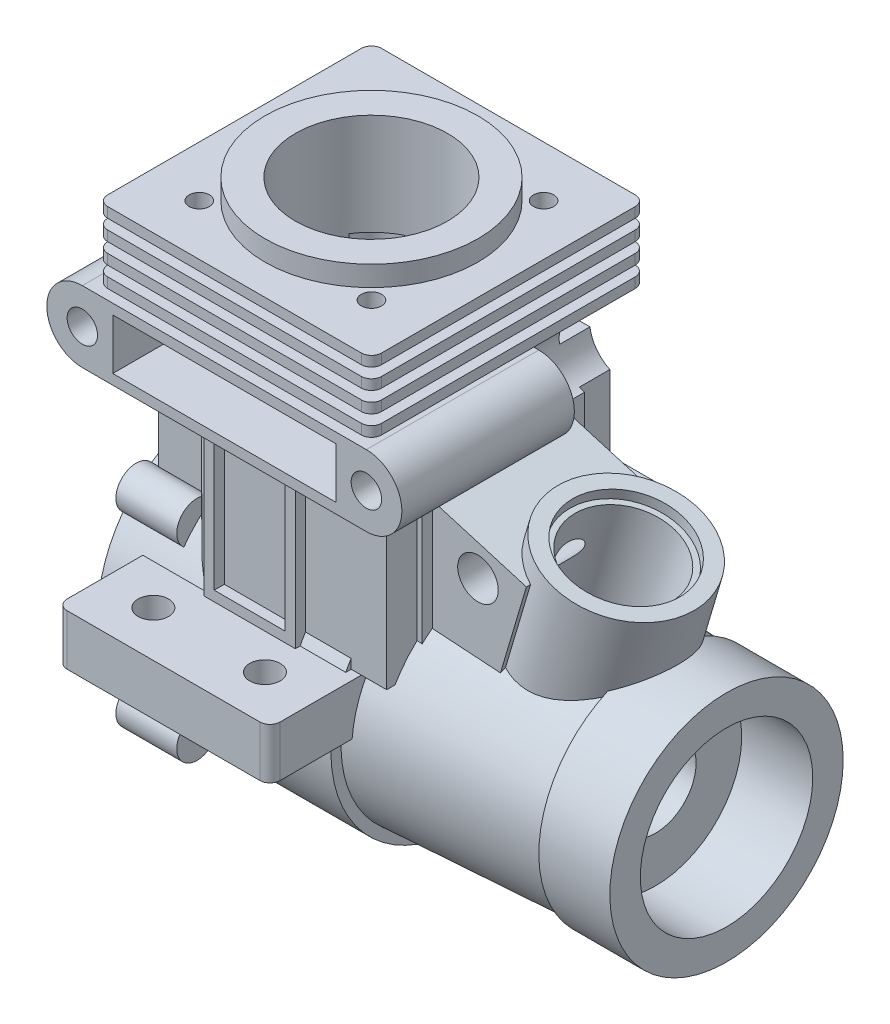
SolidWorks part; units mm, degrees
material "Gray Cast Iron"
ref_plane "Front" through (0, 0, 0) normal (0, 0, 1) x (1, 0, 0)
ref_plane "Top" through (0, 0, 0) normal (0, 1, 0) x (1, 0, 0)
ref_plane "Right" through (0, 0, 0) normal (1, 0, 0) x (0, 0, -1)
sketch "Sketch1" plane through (0, 0, 0) normal (0, 1, 0) x (1, 0, 0)
  line L1 (-13.5, 13.5) -> (13.5, 13.5)
  line L2 (-13.5, 13.5) -> (-13.5, -13.5)
  line L3 (-13.5, -13.5) -> (13.5, -13.5)
  line L4 (13.5, 13.5) -> (13.5, -13.5)
  line L5 (-13.5, 13.5) -> (13.5, -13.5) construction
  line L6 (-13.5, -13.5) -> (13.5, 13.5) construction
  point P0 (0, 0)
extrude "Boss-Extrude2" add sketch "Sketch1" along normal blind 1
sketch "Sketch3" plane through (0, 1, 0) normal (0, 1, 0) x (1, 0, 0)
  line L1 (11.5, 11.5) -> (-11.5, 11.5)
  line L2 (11.5, 11.5) -> (11.5, -11.5)
  line L3 (11.5, -11.5) -> (-11.5, -11.5)
  line L4 (-11.5, 11.5) -> (-11.5, -11.5)
  line L5 (11.5, 11.5) -> (-11.5, -11.5) construction
  line L6 (11.5, -11.5) -> (-11.5, 11.5) construction
  point P0 (0, 0)
extrude "Boss-Extrude3" add sketch "Sketch3" along normal blind 1
sketch "Sketch4" plane through (0, 2, 0) normal (0, 1, 0) x (1, 0, 0)
  line L1 (13.5, -13.5) -> (-13.5, -13.5)
  line L2 (13.5, -13.5) -> (13.5, 13.5)
  line L3 (13.5, 13.5) -> (-13.5, 13.5)
  line L4 (-13.5, -13.5) -> (-13.5, 13.5)
  line L5 (13.5, -13.5) -> (-13.5, 13.5) construction
  line L6 (13.5, 13.5) -> (-13.5, -13.5) construction
  point P0 (0, 0)
extrude "Boss-Extrude4" add sketch "Sketch4" along normal blind 1
sketch "Sketch5" plane through (0, 3, 0) normal (0, 1, 0) x (1, 0, 0)
  line L1 (11.5, -11.5) -> (-11.5, -11.5)
  line L2 (11.5, -11.5) -> (11.5, 11.5)
  line L3 (11.5, 11.5) -> (-11.5, 11.5)
  line L4 (-11.5, -11.5) -> (-11.5, 11.5)
  line L5 (11.5, -11.5) -> (-11.5, 11.5) construction
  line L6 (11.5, 11.5) -> (-11.5, -11.5) construction
  point P0 (0, 0)
extrude "Boss-Extrude5" add sketch "Sketch5" along normal blind 1
sketch "Sketch6" plane through (0, 4, 0) normal (0, 1, 0) x (1, 0, 0)
  line L1 (13.5, -13.5) -> (-13.5, -13.5)
  line L2 (13.5, -13.5) -> (13.5, 13.5)
  line L3 (13.5, 13.5) -> (-13.5, 13.5)
  line L4 (-13.5, -13.5) -> (-13.5, 13.5)
  line L5 (13.5, -13.5) -> (-13.5, 13.5) construction
  line L6 (13.5, 13.5) -> (-13.5, -13.5) construction
  point P0 (0, 0)
extrude "Boss-Extrude6" add sketch "Sketch6" along normal blind 1
sketch "Sketch7" plane through (0, 5, 0) normal (0, 1, 0) x (1, 0, 0)
  line L1 (11.5, -11.5) -> (-11.5, -11.5)
  line L2 (11.5, -11.5) -> (11.5, 11.5)
  line L3 (11.5, 11.5) -> (-11.5, 11.5)
  line L4 (-11.5, -11.5) -> (-11.5, 11.5)
  line L5 (11.5, -11.5) -> (-11.5, 11.5) construction
  line L6 (11.5, 11.5) -> (-11.5, -11.5) construction
  point P0 (0, 0)
  dimension "D1" = 23
  dimension "D2" = 23
extrude "Boss-Extrude7" add sketch "Sketch7" along normal blind 1
sketch "Sketch8" plane through (0, 6, 0) normal (0, 1, 0) x (1, 0, 0)
  line L1 (13.5, -13.5) -> (-13.5, -13.5)
  line L2 (13.5, -13.5) -> (13.5, 13.5)
  line L3 (13.5, 13.5) -> (-13.5, 13.5)
  line L4 (-13.5, -13.5) -> (-13.5, 13.5)
  line L5 (13.5, -13.5) -> (-13.5, 13.5) construction
  line L6 (13.5, 13.5) -> (-13.5, -13.5) construction
  point P0 (0, 0)
extrude "Boss-Extrude8" add sketch "Sketch8" along normal blind 1
fillet "Fillet1" radius 1 28 edges at (-13.5, 0.5, 13.5) (-11.5, 1.5, 11.5) (-13.5, 2.5, 13.5) (-11.5, 3.5, 11.5) (-13.5, 4.5, 13.5) (-11.5, 5.5, 11.5) (-13.5, 6.5, 13.5) (13.5, 0.5, 13.5) (11.5, 1.5, 11.5) (13.5, 2.5, 13.5) (11.5, 3.5, 11.5) (13.5, 4.5, 13.5) (11.5, 5.5, 11.5) (13.5, 6.5, 13.5) (13.5, 0.5, -13.5) (11.5, 1.5, -11.5) (13.5, 2.5, -13.5) (11.5, 3.5, -11.5) (13.5, 4.5, -13.5) (11.5, 5.5, -11.5) (13.5, 6.5, -13.5) (-13.5, 0.5, -13.5) (-11.5, 1.5, -11.5) (-13.5, 2.5, -13.5) (-11.5, 3.5, -11.5) (-13.5, 4.5, -13.5) (-11.5, 5.5, -11.5) (-13.5, 6.5, -13.5)
ref_plane "Plane1" through (0, 0, 14.5) normal (0, 0, 1) x (1, 0, 0)
sketch "Sketch10" plane through (0, 0, 14.5) normal (0, 0, 1) x (1, 0, 0)
  line L3 (-14, -3.5) -> (14, -3.5) construction
  line L4 (-14, 0) -> (14, 0)
  line L5 (-14, -7) -> (14, -7)
  arc A0 (-14, 0) -> (-14, -7) centre (-14, -3.5) ccw
  arc A1 (14, -7) -> (14, 0) centre (14, -3.5) ccw
  point P5 (0, -3.5)
extrude "Boss-Extrude11" add sketch "Sketch10" against normal blind 17
sketch "Sketch12" plane through (0, 0, 14.5) normal (0, 0, 1) x (1, 0, 0)
  line L0 (0, 0) -> (0, -3.5) construction
  line L1 (0, -3.5) -> (14, -3.5) construction
  line L2 (0, -3.5) -> (-14, -3.5) construction
  circle A0 centre (-14, -3.5) radius 1.5
  circle A1 centre (14, -3.5) radius 1.5
  dimension "D1" = 3.5
  dimension "D2" = 14
  dimension "D3" = 14
extrude "Cut-Extrude1" cut sketch "Sketch12" against normal blind 17
ref_plane "Plane2" through (0, -7, 0) normal (0, -1, 0) x (-1, 0, 0)
sketch "Sketch13" plane through (0, -7, 0) normal (0, -1, 0) x (-1, 0, 0)
  line L1 (-13, 8) -> (13, 8)
  line L2 (-13, 8) -> (-13, -8)
  line L3 (-13, -8) -> (13, -8)
  line L4 (13, 8) -> (13, -8)
  line L5 (-13, 8) -> (13, -8) construction
  line L6 (-13, -8) -> (13, 8) construction
  point P0 (0, 0)
extrude "Boss-Extrude13" add sketch "Sketch13" along normal blind 22 and the other way blind 7
ref_plane "Plane4" through (0, 0, -8) normal (0, 0, -1) x (-1, 0, 0)
sketch "Sketch16" plane through (0, 0, -8) normal (0, 0, -1) x (-1, 0, 0)
  circle A0 centre (-14, -3.5) radius 3.5
  circle A1 centre (14, -3.5) radius 3.5
extrude "Cut-Extrude2" cut sketch "Sketch16" against normal blind 5.5
ref_plane "Plane7" through (0, -1, 0) normal (0, -1, 0) x (-1, 0, 0)
sketch "Sketch21" plane through (0, -1, 0) normal (0, -1, 0) x (-1, 0, 0)
  line L1 (13, 8) -> (-13, 8) construction
  line L3 (-9.5, 8) -> (-9.5, 13.5)
  line L4 (-12.5, 13.5) -> (12.5, 13.5) construction
  line L5 (-9.5, 13.5) -> (9.5, 13.5)
  line L6 (9.5, 13.5) -> (9.5, 8)
  line L7 (-9.5, 8) -> (9.5, 8)
extrude "Boss-Extrude16" add sketch "Sketch21" along normal blind 1
ref_plane "Plane8" through (0, -3, 0) normal (0, -1, 0) x (-1, 0, 0)
sketch "Sketch22" plane through (0, -3, 0) normal (0, -1, 0) x (-1, 0, 0)
  line L0 (-9.5, 8) -> (-9.5, 13.5)
  line L1 (13, 8) -> (-13, 8) construction
  line L2 (-9.5, 8) -> (9.5, 8) construction
  line L3 (9.5, 13.5) -> (-9.5, 13.5) construction
  line L4 (-9.5, 13.5) -> (-9.5, 8) construction
  line L5 (-9.5, 13.5) -> (9.5, 13.5)
  line L6 (-12.5, 13.5) -> (12.5, 13.5) construction
  line L7 (9.5, 13.5) -> (9.5, 8)
  line L8 (13, 8) -> (-13, 8) construction
  line L9 (9.5, 8) -> (-9.5, 8)
extrude "Boss-Extrude17" add sketch "Sketch22" along normal blind 1
fillet "Fillet2" radius 1 4 edges at (9.5, -3.5, -13.5) (9.5, -1.5, -13.5) (-9.5, -1.5, -13.5) (-9.5, -3.5, -13.5)
sketch "Sketch24" plane through (0, 0, -8) normal (0, 0, -1) x (-1, 0, 0)
  line L0 (-4.5, -4) -> (-4.5, -23)
  line L1 (8.5, -4) -> (-8.5, -4) construction
  line L2 (4.5, -4) -> (4.5, -23)
  line L4 (4.5, -23) -> (-4.5, -23)
  line L5 (-4.5, -4) -> (4.5, -4)
  dimension "D1" = 19
  dimension "D2" = 9
extrude "Boss-Extrude18" add sketch "Sketch24" along normal blind 4
sketch "Sketch25" plane through (0, 0, -12) normal (0, 0, -1) x (-1, 0, 0)
  line L0 (-3.5, -22) -> (3.5, -22)
  line L1 (3.5, -22) -> (3.5, -5)
  line L2 (3.5, -5) -> (-3.5, -5)
  line L3 (-3.5, -5) -> (-3.5, -22)
  line L4 (-4.5, -4) -> (-4.5, -23) construction
  line L5 (4.5, -23) -> (4.5, -4) construction
  line L6 (-4.5, -23) -> (4.5, -23) construction
  line L7 (4.5, -4) -> (-4.5, -4) construction
  dimension "D1" = 1
  dimension "D2" = 1
  dimension "D3" = 1
  dimension "D4" = 1
extrude "Cut-Extrude3" cut sketch "Sketch25" against normal blind 1
sketch "Sketch26" plane through (0, 0, 14.5) normal (0, 0, 1) x (1, 0, 0)
  circle A0 centre (-14, -3.5) radius 1.5
  circle A1 centre (14, -3.5) radius 1.5
extrude "Cut-Extrude4" cut sketch "Sketch26" against normal through all
sketch "Sketch27" plane through (0, -7, 0) normal (0, -1, 0) x (1, 0, 0)
  line L0 (4.5, 8) -> (-4.5, 8)
  line L2 (4.5, -12) -> (4.5, 8) construction
  line L3 (13, 8) -> (-13, 8) construction
  line L4 (-4.5, 8) -> (-4.5, 12)
  line L5 (-4.5, 12) -> (4.5, 12)
  line L6 (4.5, 12) -> (4.5, 8)
  dimension "D1" = 9
  dimension "D2" = 4
extrude "Boss-Extrude20" add sketch "Sketch27" along normal blind 16
sketch "Sketch29" plane through (0, 0, 12) normal (0, 0, 1) x (1, 0, 0)
  line L0 (-3.5, -8) -> (-3.5, -22)
  line L1 (-3.5, -22) -> (3.5, -22)
  line L2 (3.5, -22) -> (3.5, -8)
  line L3 (3.5, -8) -> (-3.5, -8)
  line L4 (-4.5, -23) -> (-4.5, -7) construction
  line L5 (4.5, -23) -> (-4.5, -23) construction
  line L6 (4.5, -23) -> (4.5, -7) construction
  line L7 (-14, -7) -> (14, -7) construction
  dimension "D1" = 1
  dimension "D2" = 1
  dimension "D3" = 1
  dimension "D4" = 1
extrude "Cut-Extrude6" cut sketch "Sketch29" against normal blind 1
ref_plane "Plane14" through (0, -4, 0) normal (0, -1, 0) x (-1, 0, 0)
sketch "Sketch30" plane through (0, -4, 0) normal (0, -1, 0) x (-1, 0, 0)
  line L1 (4.5, 8) -> (8.1408, 8)
  line L2 (13, 8) -> (-13, 8) construction
  line L3 (4.5, 8) -> (4.5, 11.6408)
  line L4 (4.5, 12) -> (4.5, 8) construction
  arc A1 (4.5, 11.6408) -> (8.1408, 8) centre (0.9645, 4.4645) cw
  dimension "D1" = 5
extrude "Boss-Extrude22" add sketch "Sketch30" along normal blind 19
sketch "Sketch32" plane through (0, -7, 0) normal (0, -1, 0) x (1, 0, 0)
  line L0 (-4.5, 8) -> (-0.9645, 4.4645) construction
  line L1 (-4.5, 8) -> (-4.5, 11.6408)
  line L2 (-4.5, 8) -> (-8.1408, 8)
  line L3 (-4.5, 8) -> (-13, 8) construction
  arc A1 (-8.1408, 8) -> (-4.5, 11.6408) centre (-0.9645, 4.4645) cw
  line M2 (-13, 8) -> (-4.5, 8)
  line M3 (-4.5, 8) -> (-4.5, 12)
  dimension "D1" = 5
extrude "Boss-Extrude23" add sketch "Sketch32" along normal blind 16 contours A1 M2 M3 region at (-5.8456, -7, 9.3456)
sketch "Sketch33" plane through (0, -7, 0) normal (0, -1, 0) x (1, 0, 0)
  line L0 (4.5, 8) -> (4.5, 11)
  line L1 (4.5, 8) -> (4.5, 12) construction
  line L4 (13, 8) -> (4.5, 8) construction
  line L5 (13, 8) -> (-13, 8) construction
  line L6 (12.5, 8) -> (4.5, 8)
  line L8 (4.5, 11) -> (12.5, 11)
  line L9 (12.5, 11) -> (12.5, 8)
  dimension "D1" = 3
  dimension "D2" = 8
extrude "Boss-Extrude24" add sketch "Sketch33" along normal blind 16
sketch "Sketch34" plane through (0, -4, 0) normal (0, -1, 0) x (1, 0, 0)
  line L0 (4.5, -8) -> (12.5, -8)
  line L1 (-13, -8) -> (13, -8) construction
  line L6 (4.5, -8) -> (4.5, -11)
  line L7 (4.5, -11) -> (12.5, -11)
  line L8 (12.5, -11) -> (12.5, -8)
  dimension "D2" = 8
extrude "Boss-Extrude25" add sketch "Sketch34" along normal blind 19
sketch "Sketch35" plane through (0, 0, -2.5) normal (0, 0, -1) x (-1, 0, 0)
  circle A0 centre (-14, -3.5) radius 3.5
extrude "Cut-Extrude7" cut sketch "Sketch35" along normal blind 19
sketch "Sketch37" plane through (-13, 0, 0) normal (-1, 0, 0) x (0, 0, 1)
  line L0 (8, -29) -> (-8, -29) construction
  circle A0 centre (0, -29) radius 13
extrude "Boss-Extrude27" add sketch "Sketch37" against normal blind 22 and the other way blind 1
sketch "Sketch38" plane through (9, 0, 0) normal (1, 0, 0) x (0, 0, -1)
  line L0 (8, -29) -> (-8, -29) construction
  circle A0 centre (0, -29) radius 12
extrude "Boss-Extrude29" add sketch "Sketch38" along normal blind 19 draft 3
sketch "Sketch47" plane through (28, 0, 0) normal (1, 0, 0) x (0, 0, -1)
  circle A0 centre (0, -29) radius 11.5
extrude "Boss-Extrude31" add sketch "Sketch47" along normal blind 7
ref_plane "Plane28" through (0, 0, 0) normal (0, 0, 1) x (1, 0, 0)
sketch "Sketch49" plane through (0, 0, 0) normal (0, 0, 1) x (1, 0, 0)
  line L0 (28, -17.5) -> (20, -17.5) construction
  line L1 (20.2733, -26.3868) -> (25.1048, -10.0878)
  line L2 (25.1048, -10.0878) -> (31.8162, -12.0772)
  line L3 (31.8162, -12.0772) -> (26.9847, -28.3762)
  line L4 (26.9847, -28.3762) -> (20.2733, -26.3868)
  dimension "D1" = 8
  dimension "D2" = 9
  dimension "D3" = 17
  dimension "D4" = 7
revolve "Revolve3" add sketch "Sketch49" angle 360 about L1
sketch "Sketch51" plane through (0, 0, 0) normal (0, 0, 1) x (1, 0, 0)
  line L0 (9.7011, -7.6077) -> (4.7226, -24.4028)
  line L1 (31.8162, -12.0772) -> (18.3935, -8.0984) construction
  line L2 (22.272, -11.3341) -> (9.7011, -7.6077)
  line L3 (22.272, -11.3341) -> (17.2935, -28.1291)
  line L4 (17.2935, -28.1291) -> (4.7226, -24.4028)
  dimension "D1" = 2
extrude "Boss-Extrude33" add sketch "Sketch51" along normal blind 7 and the other way blind 7
sketch "Sketch52" plane through (-14, 0, 0) normal (-1, 0, 0) x (0, 0, 1)
  line L1 (9.1924, -19.8076) -> (-9.1924, -38.1924) construction
  line L2 (-9.1924, -19.8076) -> (9.1924, -38.1924) construction
  circle A0 centre (0, -29) radius 13 construction
  circle A1 centre (-9.1924, -19.8076) radius 2
  circle A2 centre (-9.1924, -38.1924) radius 2
  circle A3 centre (9.1924, -38.1924) radius 2
  circle A4 centre (9.1924, -19.8076) radius 2
extrude "Boss-Extrude34" add sketch "Sketch52" against normal blind 6
sketch "Sketch53" plane through (0, 7, 0) normal (0, 1, 0) x (1, 0, 0)
  circle A0 centre (0, 0) radius 10.5
extrude "Boss-Extrude35" add sketch "Sketch53" along normal blind 2
sketch "Sketch54" plane through (0, 9, 0) normal (0, 1, 0) x (1, 0, 0)
  circle A0 centre (0, 0) radius 7.5
  dimension "D1" = 15
sketch "Sketch55" plane through (35, 0, 0) normal (1, 0, 0) x (0, 0, -1)
  circle A0 centre (0, -29) radius 4
extrude "Cut-Extrude13" cut sketch "Sketch55" against normal through all
sketch "Sketch57" plane through (35, 0, 0) normal (1, 0, 0) x (0, 0, -1)
  circle A0 centre (0, -29) radius 8.5
extrude "Cut-Extrude14" cut sketch "Sketch57" against normal blind 7
sketch "Sketch58" plane through (-14, 0, 0) normal (-1, 0, 0) x (0, 0, 1)
  circle A0 centre (0, -29) radius 10.5
extrude "Cut-Extrude15" cut sketch "Sketch58" against normal blind 20
sketch "Sketch59" plane through (-14, 0, 0) normal (-1, 0, 0) x (0, 0, 1)
  circle A0 centre (0, -29) radius 11
extrude "Cut-Extrude16" cut sketch "Sketch59" against normal blind 15
sketch "Sketch60" plane through (-14, 0, 0) normal (-1, 0, 0) x (0, 0, 1)
  circle A0 centre (0, -29) radius 11
  dimension "D1" = 22
extrude "Boss-Extrude36" add sketch "Sketch60" against normal blind 9
sketch "Sketch61" plane through (-14, 0, 0) normal (-1, 0, 0) x (0, 0, 1)
  circle A0 centre (0, -29) radius 10.5
extrude "Cut-Extrude17" cut sketch "Sketch61" against normal blind 9
sketch "Sketch62" plane through (6, 0, 0) normal (-1, 0, 0) x (0, 0, 1)
  circle A0 centre (0, -29) radius 8.5
extrude "Cut-Extrude18" cut sketch "Sketch62" against normal blind 7
sketch "Sketch63" plane through (-0.721, -2.4323, 0) normal (0.2842, 0.9588, 0) x (0.9588, -0.2842, 0)
  circle A0 centre (26.9366, 0) radius 5
extrude "Cut-Extrude19" cut sketch "Sketch63" against normal blind 20 draft 3
extrude "Cut-Extrude20" cut sketch "Sketch54" against normal blind 40 contours A0
sketch "Sketch64" plane through (0, 0, 14.5) normal (0, 0, 1) x (1, 0, 0)
  line L0 (-14, -3.5) -> (14, -3.5) construction
  line L1 (2, -1) -> (2, -6)
  line L2 (-11, -1) -> (11, -1)
  line L3 (-11, -1) -> (-11, -6)
  line L4 (-11, -6) -> (11, -6)
  line L5 (11, -1) -> (11, -6)
  line L6 (-11, -1) -> (11, -6) construction
  line L7 (-11, -6) -> (11, -1) construction
  point P4 (0, -3.5)
  dimension "D1" = 22
  dimension "D2" = 5
  dimension "D3" = 9
extrude "Cut-Extrude21" cut sketch "Sketch64" against normal blind 5 contours L5 L2 L1 L4 region at (6.5, -3.5, 14.5)
sketch "Sketch65" plane through (0, 0, 14.5) normal (0, 0, 1) x (1, 0, 0)
  line L0 (2, -1) -> (-11, -1)
  line L1 (2, -1) -> (2, -6)
  line L2 (2, -6) -> (-11, -6)
  line L3 (-11, -6) -> (-11, -1)
  dimension "D1" = 13
extrude "Cut-Extrude22" cut sketch "Sketch65" against normal blind 13
sketch "Sketch66" plane through (0, 9, 0) normal (0, 1, 0) x (1, 0, 0)
  line L0 (-5, 5.5902) -> (5, 5.5902) construction
  line L1 (5, 5.5902) -> (5, -5.5902) construction
  arc A0 (6, 4.5) -> (1, 7.433) centre (0, 0) ccw construction
  arc A1 (1, -7.433) -> (6, -4.5) centre (0, 0) ccw construction
  circle A2 centre (-5, 5.5902) radius 2
  circle A3 centre (5, 5.5902) radius 2
  circle A4 centre (5, -5.5902) radius 2
extrude "Cut-Extrude23" cut sketch "Sketch66" against normal blind 35
sketch "Sketch67" plane through (0, 9, 0) normal (0, 1, 0) x (1, 0, 0)
  arc A0 (-6.2996, 4.07) -> (-3.3448, 6.7128) centre (0, 0) cw
  arc A1 (-3.3448, 6.7128) -> (-6.2996, 4.07) centre (-5, 5.5902) ccw construction
  arc A2 (3.3448, 6.7128) -> (6.2996, 4.07) centre (0, 0) cw
  arc A3 (6.2996, 4.07) -> (3.3448, 6.7128) centre (5, 5.5902) ccw construction
  arc A4 (6.2996, -4.07) -> (3.3448, -6.7128) centre (0, 0) cw
  arc A5 (3.3448, -6.7128) -> (6.2996, -4.07) centre (5, -5.5902) ccw construction
  arc A6 (-6.6457, 4.4536) -> (-3.6876, 7.0994) centre (0, 0) cw
  arc A7 (-5, 7.5902) -> (-6.2996, 4.07) centre (-5, 5.5902) ccw construction
  arc A8 (-3.3448, 6.7128) -> (-5, 7.5902) centre (-5, 5.5902) ccw construction
  arc A9 (3.7729, 7.1694) -> (6.6682, 4.4869) centre (-0.0485, 0.1411) cw
  arc A10 (6, 7.3222) -> (3.3448, 6.7128) centre (5, 5.5902) ccw construction
  arc A11 (6.6457, -4.4536) -> (3.6876, -7.0994) centre (0, 0) cw
  arc A12 (3.3448, -6.7128) -> (6, -7.3222) centre (5, -5.5902) ccw construction
  arc M1 (-6.2996, 4.07) -> (-3.3448, 6.7128) centre (-5, 5.5902) cw
  arc M3 (3.3448, 6.7128) -> (6.2996, 4.07) centre (5, 5.5902) cw
  arc M5 (6.2996, -4.07) -> (3.3448, -6.7128) centre (5, -5.5902) cw
extrude "Boss-Extrude37" add sketch "Sketch67" against normal blind 27 contours A6 A0 M1 | A9 A2 M3 | A11 A4 M5 region at (-5.1085, 9, -5.7115) region at (5.1051, 9, -5.7631) region at (5.1085, 9, 5.7115)
sketch "Sketch68" plane through (0, 9, 0) normal (0, 1, 0) x (1, 0, 0)
  circle A0 centre (-5, 5.5902) radius 2
  circle A1 centre (5, 5.5902) radius 2
  circle A2 centre (5, -5.5902) radius 2
extrude "Cut-Extrude24" cut sketch "Sketch68" against normal blind 15
sketch "Sketch69" plane through (0, 9, 0) normal (0, 1, 0) x (1, 0, 0)
  arc A0 (-6.2996, 4.07) -> (-3.3448, 6.7128) centre (0, 0) cw
  arc A1 (3.3448, 6.7128) -> (6.2996, 4.07) centre (0, 0) cw
  arc A2 (6.2996, 4.07) -> (3.3448, 6.7128) centre (5, 5.5902) ccw construction
  arc A3 (6.2996, -4.07) -> (3.3448, -6.7128) centre (0, 0) cw
  arc A4 (3.3448, -6.7128) -> (6.2996, -4.07) centre (5, -5.5902) ccw construction
  arc A5 (-3.3448, 6.7128) -> (-6.2996, 4.07) centre (-5, 5.5902) ccw construction
  arc M1 (-6.2996, 4.07) -> (-3.3448, 6.7128) centre (-5, 5.5902) cw
  arc M3 (3.3448, 6.7128) -> (6.2996, 4.07) centre (5, 5.5902) cw
  arc M5 (6.2996, -4.07) -> (3.3448, -6.7128) centre (5, -5.5902) cw
extrude "Boss-Extrude38" add sketch "Sketch69" against normal blind 10 contours A0 M1 | A1 M3 | A3 M5 region at (-5.5327, 9, -6.1857) region at (5.5327, 9, -6.1857) region at (5.5327, 9, 6.1857)
sketch "Sketch70" plane through (-0.721, -2.4323, 0) normal (0.2842, 0.9588, 0) x (0.9588, -0.2842, 0)
  circle A0 centre (26.9366, 0) radius 5.5
extrude "Cut-Extrude25" cut sketch "Sketch70" against normal blind 1
sketch "Sketch71" plane through (-14, 0, 0) normal (-1, 0, 0) x (0, 0, 1)
  circle A0 centre (-9.1924, -19.8076) radius 1
  circle A1 centre (9.1924, -19.8076) radius 1
  circle A2 centre (9.1924, -38.1924) radius 1
  circle A3 centre (-9.1924, -38.1924) radius 1
extrude "Cut-Extrude26" cut sketch "Sketch71" against normal blind 4
cosmetic thread "Cosmetic Thread1" parameters "D2"=2.5
cosmetic thread "Cosmetic Thread2" parameters "D2"=2.5
cosmetic thread "Cosmetic Thread3" parameters "D2"=2.5
cosmetic thread "Cosmetic Thread4" parameters "D2"=2.5
sketch "Sketch72" plane through (0, 0, 7) normal (0, 0, 1) x (1, 0, 0)
  line L1 (35, -40.5) -> (35, -17.5) construction
  line L2 (35, -17.5) -> (30.2086, -17.5) construction
  circle A0 centre (17.5, -13) radius 2
  dimension "D1" = 4.5
  dimension "D2" = 17.5
extrude "Cut-Extrude27" cut sketch "Sketch72" against normal through all
sketch "Sketch73" plane through (0, 9, 0) normal (0, 1, 0) x (1, 0, 0)
  circle A1 centre (-8.4853, 8.4853) radius 1
  circle A2 centre (8.4853, 8.4853) radius 1
  circle A3 centre (8.4853, -8.4853) radius 1
  circle A4 centre (-8.4853, -8.4853) radius 1
  point P11 (0, 0)
  dimension "D1" = 4
extrude "Cut-Extrude28" cut sketch "Sketch73" against normal blind 8
cosmetic thread "Cosmetic Thread5" parameters "D2"=2.5
cosmetic thread "Cosmetic Thread6" parameters "D2"=2.5
cosmetic thread "Cosmetic Thread7" parameters "D2"=2.5
cosmetic thread "Cosmetic Thread8" parameters "D2"=2.5
ref_plane "Plane5" through (0, 0, -8) normal (0, 0, -1) x (-1, 0, 0)
sketch "Sketch74" plane through (0, 0, -8) normal (0, 0, -1) x (-1, 0, 0)
  line L0 (-10, -23) -> (11, -23)
  line L1 (-4.5, -23) -> (4.5, -23) construction
  line L2 (-10, -23) -> (-10, -28)
  line L3 (-10, -28) -> (11, -28)
  line L4 (11, -28) -> (11, -23)
  line L5 (14, -36.6736) -> (14, -21.3264) construction
  dimension "D1" = 5
  dimension "D2" = 21
  dimension "D3" = 3
extrude "Boss-Extrude39" add sketch "Sketch74" along normal blind 12 and the other way blind 28
fillet "Fillet6" radius 1 4 edges at (-11, -25.5, 20) (10, -25.5, 20) (-11, -25.5, -20) (10, -25.5, -20)
sketch "Sketch75" plane through (-14, 0, 0) normal (-1, 0, 0) x (0, 0, 1)
  circle A0 centre (0, -29) radius 10.5
extrude "Cut-Extrude30" cut sketch "Sketch75" against normal blind 24
sketch "Sketch76" plane through (10, 0, 0) normal (-1, 0, 0) x (0, 0, 1)
  circle A0 centre (0, -29) radius 8.5
  circle A1 centre (0, -29) radius 10.5
extrude "Boss-Extrude40" add sketch "Sketch76" along normal blind 2
sketch "Sketch77" plane through (-14, 0, 0) normal (-1, 0, 0) x (0, 0, 1)
  circle A0 centre (0, -29) radius 11
extrude "Cut-Extrude32" cut sketch "Sketch77" against normal blind 15
sketch "Sketch78" plane through (-14, 0, 0) normal (-1, 0, 0) x (0, 0, 1)
  circle A0 centre (0, -29) radius 11
  circle A1 centre (0, -29) radius 10.5
extrude "Boss-Extrude41" add sketch "Sketch78" against normal blind 9
sketch "Sketch79" plane through (0, -23, 0) normal (0, 1, 0) x (1, 0, 0)
  line L6 (-12.7676, 0) -> (15.5776, 0) construction
  circle A0 centre (-6, 15.5) radius 1.5
  circle A1 centre (5, 15.5) radius 1.5
  circle A2 centre (5, -15.5) radius 1.5
  circle A3 centre (-6, -15.5) radius 1.5
extrude "Cut-Extrude33" cut sketch "Sketch79" against normal blind 5
